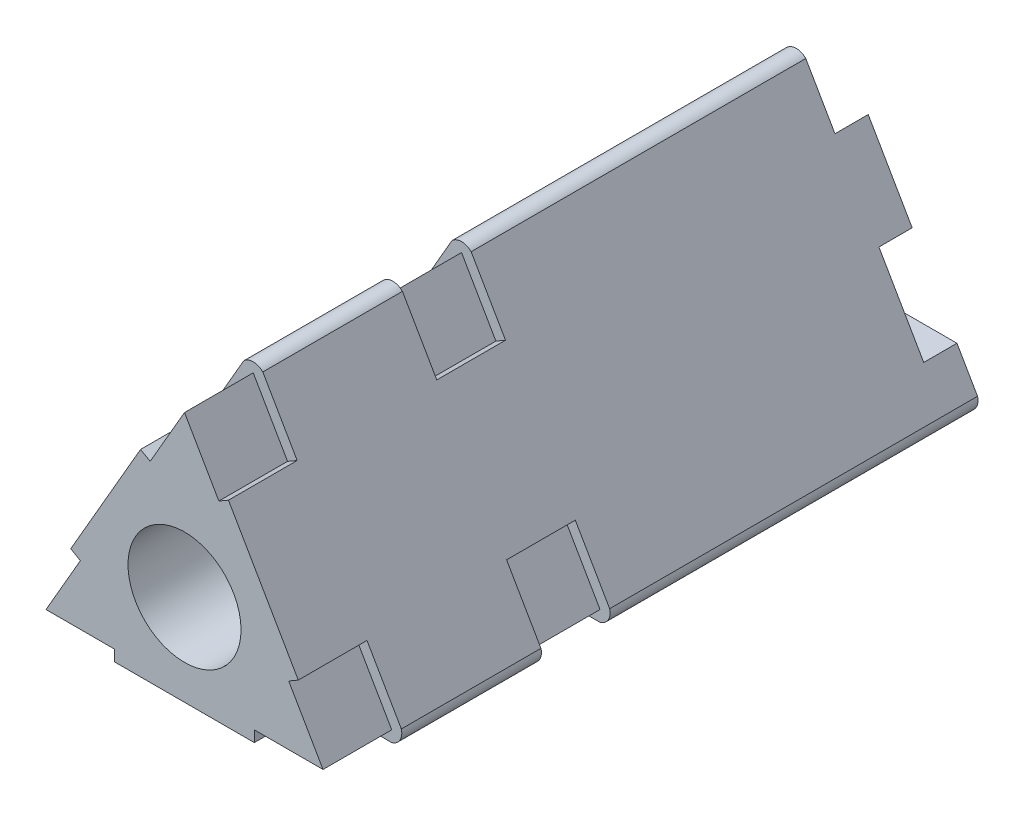
SolidWorks part; units mm, degrees
ref_plane "正面" through (0, 0, 0) normal (0, 0, 1) x (1, 0, 0)
ref_plane "平面" through (0, 0, 0) normal (0, 1, 0) x (1, 0, 0)
ref_plane "右側面" through (0, 0, 0) normal (1, 0, 0) x (0, 0, -1)
sketch "ｽｹｯﾁ1" plane through (0, 0, 0) normal (0, 0, 1) x (1, 0, 0)
  line L0 (0, 21.6506) -> (-12.5, 0)
  line L1 (-12.5, 0) -> (12.5, 0)
  line L2 (12.5, 0) -> (0, 21.6506)
  dimension "D1" = 25
extrude "ﾎﾞｽ - 押し出し1" add sketch "ｽｹｯﾁ1" along normal blind 58.2
sketch "ｽｹｯﾁ2" plane through (-9.375, 5.4127, 0) normal (-0.866, 0.5, 0) x (0, 0, 1)
  line L0 (58.2, -6.25) -> (0, -6.25) construction
  line L1 (58.2, -6.25) -> (52, -6.25)
  line L2 (58.2, -6.25) -> (58.2, -0.05)
  line L3 (58.2, -0.05) -> (52, -0.05)
  line L4 (52, -6.25) -> (52, -0.05)
  line L5 (58.2, 18.75) -> (52, 18.75)
  line L6 (58.2, 18.75) -> (58.2, 12.55)
  line L7 (58.2, 12.55) -> (52, 12.55)
  line L8 (52, 18.75) -> (52, 12.55)
  line L9 (39.4, -6.25) -> (33.2, -6.25)
  line L10 (39.4, -6.25) -> (39.4, -0.05)
  line L11 (39.4, -0.05) -> (33.2, -0.05)
  line L12 (33.2, -6.25) -> (33.2, -0.05)
  line L13 (58.2, 18.75) -> (0, 18.75) construction
  line L14 (39.4, 18.75) -> (33.2, 18.75)
  line L15 (39.4, 18.75) -> (39.4, 12.55)
  line L16 (39.4, 12.55) -> (33.2, 12.55)
  line L17 (33.2, 18.75) -> (33.2, 12.55)
  dimension "D1" = 6.2
  dimension "D2" = 6.2
  dimension "D3" = 6.2
  dimension "D4" = 6.2
  dimension "D5" = 6.2
  dimension "D6" = 6.2
  dimension "D7" = 6.2
  dimension "D8" = 6.2
  dimension "D9" = 25
sketch "ｽｹｯﾁ15" plane through (0, 0, 0) normal (0, -1, 0) x (1, 0, 0)
  line L0 (12.5, 58.2) -> (12.5, 0) construction
  line L1 (-12.5, 58.2) -> (-6.3, 58.2)
  line L2 (-12.5, 58.2) -> (-12.5, 52)
  line L3 (-12.5, 52) -> (-6.3, 52)
  line L4 (-6.3, 58.2) -> (-6.3, 52)
  line L5 (12.5, 58.2) -> (6.3, 58.2)
  line L6 (12.5, 58.2) -> (12.5, 52)
  line L7 (12.5, 52) -> (6.3, 52)
  line L8 (6.3, 58.2) -> (6.3, 52)
  line L9 (12.5, 33.2) -> (6.3, 33.2)
  line L10 (12.5, 33.2) -> (12.5, 39.4)
  line L11 (12.5, 39.4) -> (6.3, 39.4)
  line L12 (6.3, 33.2) -> (6.3, 39.4)
  line L13 (-12.5, 58.2) -> (-12.5, 0) construction
  line L14 (-12.5, 33.2) -> (-6.3, 33.2)
  line L15 (-12.5, 33.2) -> (-12.5, 39.4)
  line L16 (-12.5, 39.4) -> (-6.3, 39.4)
  line L17 (-6.3, 33.2) -> (-6.3, 39.4)
  dimension "D1" = 6.2
  dimension "D2" = 6.2
  dimension "D3" = 6.2
  dimension "D4" = 6.2
  dimension "D5" = 6.2
  dimension "D6" = 6.2
  dimension "D7" = 6.2
  dimension "D8" = 6.2
  dimension "D9" = 25
sketch "ｽｹｯﾁ20" plane through (9.375, 5.4127, 0) normal (0.866, 0.5, 0) x (0, 0, -1)
  line L0 (-58.2, -6.25) -> (0, -6.25) construction
  line L1 (-58.2, -6.25) -> (-52, -6.25)
  line L2 (-58.2, -6.25) -> (-58.2, -0.05)
  line L3 (-58.2, -0.05) -> (-52, -0.05)
  line L4 (-52, -6.25) -> (-52, -0.05)
  line L5 (-58.2, 18.75) -> (-52, 18.75)
  line L6 (-58.2, 18.75) -> (-58.2, 12.55)
  line L7 (-58.2, 12.55) -> (-52, 12.55)
  line L8 (-52, 18.75) -> (-52, 12.55)
  line L9 (-33.2, -6.25) -> (-39.4, -6.25)
  line L10 (-33.2, -6.25) -> (-33.2, -0.05)
  line L11 (-33.2, -0.05) -> (-39.4, -0.05)
  line L12 (-39.4, -6.25) -> (-39.4, -0.05)
  line L13 (-58.2, 18.75) -> (0, 18.75) construction
  line L14 (-33.2, 18.75) -> (-39.4, 18.75)
  line L15 (-33.2, 18.75) -> (-33.2, 12.55)
  line L16 (-33.2, 12.55) -> (-39.4, 12.55)
  line L17 (-39.4, 18.75) -> (-39.4, 12.55)
  dimension "D1" = 6.2
  dimension "D2" = 6.2
  dimension "D3" = 6.2
  dimension "D4" = 6.2
  dimension "D5" = 6.2
  dimension "D6" = 6.2
  dimension "D7" = 6.2
  dimension "D8" = 6.2
  dimension "D9" = 25
sketch "ｽｹｯﾁ11" plane through (0, 0, 0) normal (0, 0, -1) x (-1, 0, 0)
  line L0 (0, 21.6506) -> (12.5, 0)
  line L1 (0, 21.6506) -> (0.866, 22.1506) construction
  line L2 (-0.866, 22.1506) -> (0, 21.6506) construction
  line L3 (0.866, 22.1506) -> (13.366, 0.5)
  line L4 (12.5, 0) -> (-12.5, 0)
  line L5 (-13.366, 0.5) -> (-12.5, 0) construction
  line L6 (-12.5, 0) -> (-12.5, -1) construction
  line L7 (12.5, -1) -> (-12.5, -1)
  line L8 (0, 21.6506) -> (-12.5, 0)
  line L9 (12.5, 0) -> (12.5, -1) construction
  line L10 (12.5, 0) -> (13.366, 0.5) construction
  line L11 (-0.866, 22.1506) -> (-13.366, 0.5)
  arc A0 (-0.866, 22.1506) -> (0.866, 22.1506) centre (0, 21.2846) cw
  arc A1 (13.366, 0.5) -> (12.5, -1) centre (12.183, 0.183) cw
  arc A2 (-12.5, -1) -> (-13.366, 0.5) centre (-12.183, 0.183) cw
  dimension "D1" = 25
  dimension "D2" = 1
  dimension "D3" = 25
  dimension "D4" = 1
  dimension "D5" = 25
  dimension "D6" = 1
extrude "ﾎﾞｽ - 押し出し8" add sketch "ｽｹｯﾁ11" against normal through all
extrude "ｶｯﾄ - 押し出し5" cut sketch "ｽｹｯﾁ2" along normal blind 1
sketch "ｽｹｯﾁ16" plane through (0, 0, 52) normal (0, 0, 1) x (1, 0, 0)
  line L0 (-12.4, 0.1732) -> (-12.6732, 0.1)
  line L1 (-9.4, 5.3694) -> (-12.5, 0) construction
  line L3 (-12.6732, 0.1) -> (-12.5, 0)
  line L4 (-12.5, 0) -> (-12.4, 0.1732)
  line L7 (-13.366, 0.5) -> (-12.5, 0) construction
  dimension "D1" = 0.2
  dimension "D2" = 0.2
extrude "ﾎﾞｽ - 押し出し9" add sketch "ｽｹｯﾁ16" along normal through all and the other way through all
extrude "ｶｯﾄ - 押し出し10" cut sketch "ｽｹｯﾁ15" along normal blind 1
sketch "ｽｹｯﾁ18" plane through (0, 0, 52) normal (0, 0, 1) x (1, 0, 0)
  line L0 (-0.1732, 21.7506) -> (0, 21.6506)
  line L1 (-0.866, 22.1506) -> (0, 21.6506) construction
  line L2 (0, 21.6506) -> (-0.1, 21.4774)
  line L3 (0, 21.6506) -> (-3.1, 16.2813) construction
  line L4 (-0.1, 21.4774) -> (-0.1732, 21.7506)
  dimension "D1" = 0.2
  dimension "D2" = 0.2
extrude "ﾎﾞｽ - 押し出し10" add sketch "ｽｹｯﾁ18" against normal through all and the other way through all
sketch "ｽｹｯﾁ19" plane through (0, 0, 52) normal (0, 0, 1) x (1, 0, 0)
  line L0 (12.5, 0) -> (12.3, 0)
  line L1 (6.3, 0) -> (12.5, 0) construction
  line L2 (12.3, 0) -> (12.5, -0.2)
  line L3 (12.5, -1) -> (12.5, 0) construction
  line L4 (12.5, -0.2) -> (12.5, 0)
  dimension "D1" = 0.2
  dimension "D2" = 0.2
extrude "ﾎﾞｽ - 押し出し11" add sketch "ｽｹｯﾁ19" against normal through all and the other way through all
extrude "ｶｯﾄ - 押し出し11" cut sketch "ｽｹｯﾁ20" along normal blind 1
sketch "ｽｹｯﾁ21" plane through (0, 0, 52) normal (0, 0, 1) x (1, 0, 0)
  line L0 (0, 21.6506) -> (0.1, 21.4774)
  line L1 (3.1, 16.2813) -> (0, 21.6506) construction
  line L2 (0.1, 21.4774) -> (0.1732, 21.7506)
  line L3 (0.866, 22.1506) -> (0, 21.6506) construction
  line L4 (0.1732, 21.7506) -> (0, 21.6506)
  dimension "D1" = 0.2
  dimension "D2" = 0.2
extrude "ﾎﾞｽ - 押し出し12" add sketch "ｽｹｯﾁ21" along normal through all and the other way through all
sketch "ｽｹｯﾁ23" plane through (0, 0, 52) normal (0, 0, 1) x (1, 0, 0)
  line L0 (12.5, 0) -> (12.6732, 0.1)
  line L1 (12.6732, 0.1) -> (12.4, 0.1732)
  line L2 (12.5, 0) -> (9.4, 5.3694) construction
  line L3 (12.4, 0.1732) -> (12.5, 0)
  dimension "D1" = 0.2
  dimension "D2" = 0.2
extrude "ﾎﾞｽ - 押し出し13" add sketch "ｽｹｯﾁ23" along normal through all and the other way through all
sketch "ｽｹｯﾁ24" plane through (0, 0, 52) normal (0, 0, 1) x (1, 0, 0)
  line L0 (-12.5, 0) -> (-12.3, 0)
  line L1 (-12.5, 0) -> (-6.3, 0) construction
  line L2 (-12.3, 0) -> (-12.5, -0.2)
  line L3 (-12.5, -1) -> (-12.5, 0) construction
  line L4 (-12.5, -0.2) -> (-12.5, 0)
  dimension "D1" = 0.2
  dimension "D2" = 0.2
extrude "ﾎﾞｽ - 押し出し14" add sketch "ｽｹｯﾁ24" along normal through all and the other way through all
sketch "ｽｹｯﾁ25" plane through (0, 0, 0) normal (0, 0, -1) x (-1, 0, 0)
  line L1 (13.366, 0.5) -> (0.866, 22.1506) construction
  line L2 (0, 7.2169) -> (7.116, 11.3253) construction
  line L3 (0, 7.2169) -> (-7.116, 11.3253) construction
  line L4 (-0.866, 22.1506) -> (-13.366, 0.5) construction
  line L5 (0, 7.2169) -> (0, -1) construction
  line L6 (-12.5, -1) -> (12.5, -1) construction
  circle A0 centre (0, 7.2169) radius 4
  dimension "D1" = 8
sketch "ｽｹｯﾁ26" plane through (-6.275, 10.8686, 0) normal (-0.5, 0.866, 0) x (0.866, 0.5, 0)
  line L1 (11.8253, -33.2) -> (10.8253, -33.2)
  line L2 (11.8253, -33.2) -> (11.8253, -39.4)
  line L3 (11.8253, -39.4) -> (10.8253, -39.4)
  line L4 (10.8253, -33.2) -> (10.8253, -39.4)
extrude "ｶｯﾄ - 押し出し12" cut sketch "ｽｹｯﾁ26" along normal through all
sketch "ｽｹｯﾁ27" plane through (6.275, 10.8686, 0) normal (0.5, 0.866, 0) x (0.866, -0.5, 0)
  line L1 (-10.8253, -33.2) -> (-11.8253, -33.2)
  line L2 (-10.8253, -33.2) -> (-10.8253, -39.4)
  line L3 (-10.8253, -39.4) -> (-11.8253, -39.4)
  line L4 (-11.8253, -33.2) -> (-11.8253, -39.4)
extrude "ｶｯﾄ - 押し出し13" cut sketch "ｽｹｯﾁ27" along normal through all
sketch "ｽｹｯﾁ28" plane through (-6.275, 10.8686, 0) normal (-0.5, 0.866, 0) x (0.866, 0.5, 0)
  line L1 (11.8253, -52) -> (10.8253, -52)
  line L2 (11.8253, -52) -> (11.8253, -58.2)
  line L3 (11.8253, -58.2) -> (10.8253, -58.2)
  line L4 (10.8253, -52) -> (10.8253, -58.2)
extrude "ｶｯﾄ - 押し出し14" cut sketch "ｽｹｯﾁ28" along normal through all
sketch "ｽｹｯﾁ29" plane through (6.275, 10.8686, 0) normal (0.5, 0.866, 0) x (0.866, -0.5, 0)
  line L1 (-10.8253, -52) -> (-11.8253, -52)
  line L2 (-10.8253, -52) -> (-10.8253, -58.2)
  line L3 (-10.8253, -58.2) -> (-11.8253, -58.2)
  line L4 (-11.8253, -52) -> (-11.8253, -58.2)
extrude "ｶｯﾄ - 押し出し15" cut sketch "ｽｹｯﾁ29" along normal through all
sketch "ｽｹｯﾁ30" plane through (-0.025, -0.0433, 0) normal (-0.5, -0.866, 0) x (0.866, -0.5, 0)
  line L1 (-10.8253, 33.2) -> (-11.8253, 33.2)
  line L2 (-10.8253, 33.2) -> (-10.8253, 39.4)
  line L3 (-10.8253, 39.4) -> (-11.8253, 39.4)
  line L4 (-11.8253, 33.2) -> (-11.8253, 39.4)
extrude "ｶｯﾄ - 押し出し16" cut sketch "ｽｹｯﾁ30" along normal through all
sketch "ｽｹｯﾁ31" plane through (-6.3, 0, 0) normal (-1, 0, 0) x (0, 0, 1)
  line L1 (33.2, 0) -> (39.4, 0)
  line L2 (33.2, 0) -> (33.2, -1)
  line L3 (33.2, -1) -> (39.4, -1)
  line L4 (39.4, 0) -> (39.4, -1)
extrude "ｶｯﾄ - 押し出し17" cut sketch "ｽｹｯﾁ31" along normal through all
sketch "ｽｹｯﾁ32" plane through (-6.3, 0, 0) normal (-1, 0, 0) x (0, 0, 1)
  line L1 (52, 0) -> (58.2, 0)
  line L2 (52, 0) -> (52, -1)
  line L3 (52, -1) -> (58.2, -1)
  line L4 (58.2, 0) -> (58.2, -1)
  point P6 (0, 0)
extrude "ｶｯﾄ - 押し出し18" cut sketch "ｽｹｯﾁ32" along normal through all
sketch "ｽｹｯﾁ33" plane through (-0.025, -0.0433, 0) normal (-0.5, -0.866, 0) x (0.866, -0.5, 0)
  line L1 (-10.8253, 52) -> (-11.8253, 52)
  line L2 (-10.8253, 52) -> (-10.8253, 58.2)
  line L3 (-10.8253, 58.2) -> (-11.8253, 58.2)
  line L4 (-11.8253, 52) -> (-11.8253, 58.2)
extrude "ｶｯﾄ - 押し出し19" cut sketch "ｽｹｯﾁ33" along normal through all
sketch "ｽｹｯﾁ34" plane through (6.3, 0, 0) normal (1, 0, 0) x (0, 0, -1)
  line L1 (-52, 0) -> (-58.2, 0)
  line L2 (-52, 0) -> (-52, -1)
  line L3 (-52, -1) -> (-58.2, -1)
  line L4 (-58.2, 0) -> (-58.2, -1)
extrude "ｶｯﾄ - 押し出し20" cut sketch "ｽｹｯﾁ34" along normal through all
sketch "ｽｹｯﾁ35" plane through (6.3, 0, 0) normal (1, 0, 0) x (0, 0, -1)
  line L1 (-33.2, 0) -> (-39.4, 0)
  line L2 (-33.2, 0) -> (-33.2, -1)
  line L3 (-33.2, -1) -> (-39.4, -1)
  line L4 (-39.4, 0) -> (-39.4, -1)
extrude "ｶｯﾄ - 押し出し21" cut sketch "ｽｹｯﾁ35" along normal through all
sketch "ｽｹｯﾁ36" plane through (0.025, -0.0433, 0) normal (0.5, -0.866, 0) x (0.866, 0.5, 0)
  line L1 (10.8253, 33.2) -> (11.8253, 33.2)
  line L2 (10.8253, 33.2) -> (10.8253, 39.4)
  line L3 (10.8253, 39.4) -> (11.8253, 39.4)
  line L4 (11.8253, 33.2) -> (11.8253, 39.4)
extrude "ｶｯﾄ - 押し出し22" cut sketch "ｽｹｯﾁ36" along normal through all
sketch "ｽｹｯﾁ38" plane through (0.025, -0.0433, 0) normal (0.5, -0.866, 0) x (0.866, 0.5, 0)
  line L1 (11.8253, 52) -> (10.8253, 52)
  line L2 (11.8253, 52) -> (11.8253, 58.2)
  line L3 (11.8253, 58.2) -> (10.8253, 58.2)
  line L4 (10.8253, 52) -> (10.8253, 58.2)
extrude "ｶｯﾄ - 押し出し27" cut sketch "ｽｹｯﾁ38" along normal through all
extrude "ｶｯﾄ - 押し出し32" cut sketch "ｽｹｯﾁ25" against normal blind 3.5
sketch "ｽｹｯﾁ45" plane through (0, 0, 0) normal (0, 0, -1) x (-1, 0, 0)
  circle A0 centre (0, 7.2169) radius 5.325
  dimension "D1" = 10.65
extrude "ｶｯﾄ - 押し出し33" cut sketch "ｽｹｯﾁ45" against normal blind 3
sketch "ｽｹｯﾁ47" plane through (0, 0, 0) normal (0, 0, -1) x (-1, 0, 0)
  line L0 (3.5, 24.3557) -> (3.5, 10.7169)
  line L1 (13.0117, 10.7169) -> (3.5, 10.7169)
  line L2 (13.0117, 3.7169) -> (13.0117, 10.7169)
  line L3 (13.0117, 3.7169) -> (3.5, 3.7169)
  line L4 (-13.7285, 3.7169) -> (-13.7285, 10.7169)
  line L5 (3.5, 24.3557) -> (-3.5, 24.3557)
  line L6 (-3.5, 24.3557) -> (-3.5, 10.7169)
  line L7 (3.5, -7.4062) -> (-3.5, -7.4062)
  line L8 (-3.5, -7.4062) -> (-3.5, 3.7169)
  line L9 (3.5, -7.4062) -> (3.5, 3.7169)
  line L10 (-3.5, 3.7169) -> (-13.7285, 3.7169)
  line L11 (-3.5, 10.7169) -> (-13.7285, 10.7169)
  line L12 (0, 7.2169) -> (3.5, 3.7169) construction
  line L13 (0, 7.2169) -> (-3.5, 3.7169) construction
  line L14 (-3.5, 3.7169) -> (-3.51, 3.7416) construction
  line L15 (0, 7.2169) -> (3.5, 10.7169) construction
  line L16 (3.5, 10.7169) -> (3.5321, 10.6819) construction
  line L17 (0, 7.2169) -> (-3.5, 10.7169) construction
  dimension "D1" = 7
  dimension "D2" = 7
extrude "ｶｯﾄ - 押し出し34" cut sketch "ｽｹｯﾁ47" against normal blind 3
sketch "ｽｹｯﾁ48" plane through (0, 0, 58.2) normal (0, 0, 1) x (1, 0, 0)
  line L0 (0, 7.2169) -> (0, -1) construction
  line L1 (6.3, -1) -> (-6.3, -1) construction
  line L2 (0, 7.2169) -> (7.116, 11.3253) construction
  line L3 (3.966, 16.7813) -> (10.266, 5.8694) construction
  line L4 (0, 7.2169) -> (-7.116, 11.3253) construction
  line L5 (-10.266, 5.8694) -> (-3.966, 16.7813) construction
  circle A0 centre (0, 7.2169) radius 5.1
  dimension "D1" = 10.2
extrude "ｶｯﾄ - 押し出し35" cut sketch "ｽｹｯﾁ48" against normal blind 10
